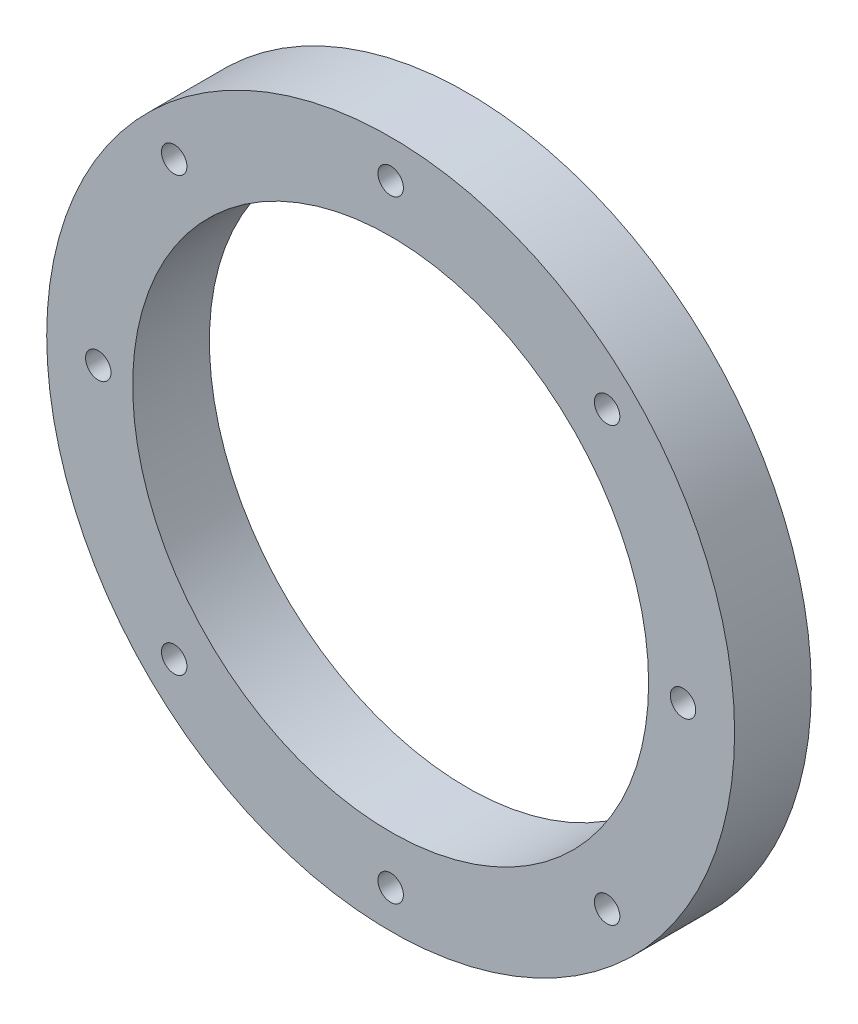
SolidWorks part; units mm, degrees
ref_plane "前视基准面" through (0, 0, 0) normal (0, 0, 1) x (1, 0, 0)
ref_plane "上视基准面" through (0, 0, 0) normal (0, 1, 0) x (1, 0, 0)
ref_plane "右视基准面" through (0, 0, 0) normal (1, 0, 0) x (0, 0, -1)
other "Configuration Table"
sketch "草图1" plane through (0, 0, 0) normal (0, 0, 1) x (1, 0, 0)
  circle A10 centre (0, 0) radius 50
  circle A11 centre (0, 0) radius 37.5
  circle A12 centre (42.5, 0) radius 1.85
  circle A13 centre (-42.5, 0) radius 1.85
  circle A14 centre (0, 44.5) radius 1.85
  circle A15 centre (31.4663, 31.4663) radius 1.85
  circle A16 centre (44.5, 0) radius 1.85
  circle A17 centre (31.4663, -31.4663) radius 1.85
  circle A18 centre (0, -44.5) radius 1.85
  circle A19 centre (-31.4663, -31.4663) radius 1.85
  circle A20 centre (-44.5, 0) radius 1.85
  circle A21 centre (-31.4663, 31.4663) radius 1.85
  point P9 (0, 0)
  point P27 (0, 0)
  dimension "D1" = 100
  dimension "D2" = 75
  dimension "D3" = 3.7
  dimension "D4" = 42.5
  dimension "D6" = 3.7
  dimension "D7" = 44.5
  dimension "D5" = 2
  dimension "D8" = 8
extrude "凸台-拉伸1" add sketch "草图1" along normal blind 11.15 contours A10 A21 A20 A13 A19 A18 A17 A16 A12 A15 A14 A11 | A12 A16 | A13 A20 region at (-48.5858, 0, 0) region at (45.0312, 0, 0) region at (-45.0312, 0, 0)
move or copy body "实体-移动/复制1" [suppressed] bodies to move or copy 106 parameters "D1"=0, "D2"=0, "D3"=0
move or copy body "实体-移动/复制2" [suppressed] bodies to move or copy 107 parameters "D1"=0, "D2"=0, "D3"=0
move or copy body "实体-移动/复制3" [suppressed] bodies to move or copy 108 parameters "D1"=0, "D2"=0, "D3"=0
move or copy body "实体-移动/复制4" [suppressed] bodies to move or copy 109 parameters "D1"=0, "D2"=0, "D3"=0
